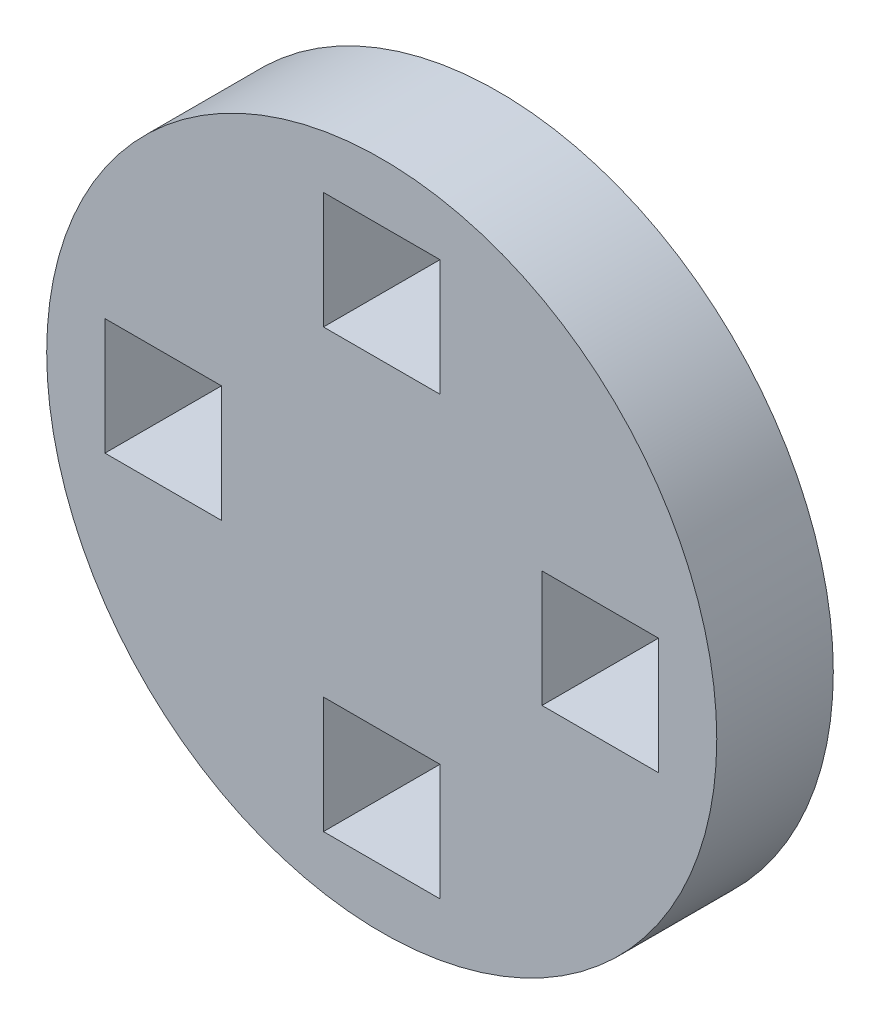
SolidWorks part; units mm, degrees
ref_plane "Front Plane" through (0, 0, 0) normal (0, 0, 1) x (1, 0, 0)
ref_plane "Top Plane" through (0, 0, 0) normal (0, 1, 0) x (1, 0, 0)
ref_plane "Right Plane" through (0, 0, 0) normal (1, 0, 0) x (0, 0, -1)
sketch "Sketch1" plane through (0, 0, 0) normal (0, 0, 1) x (1, 0, 0)
  line L0 (0, 5.5) -> (0, 0) construction
  line L1 (-2, 9.5) -> (2, 9.5)
  line L2 (-2, 9.5) -> (-2, 5.5)
  line L3 (-2, 5.5) -> (2, 5.5)
  line L4 (2, 9.5) -> (2, 5.5)
  line L5 (0, 0) -> (0, -5.5) construction
  line L6 (9.5, 2) -> (5.5, 2)
  line L7 (-2, -5.5) -> (2, -5.5)
  line L8 (-2, -5.5) -> (-2, -9.5)
  line L9 (-2, -9.5) -> (2, -9.5)
  line L10 (2, -5.5) -> (2, -9.5)
  line L11 (9.5, 2) -> (9.5, -2)
  line L12 (9.5, -2) -> (5.5, -2)
  line L13 (5.5, 2) -> (5.5, -2)
  line L14 (-5.5, 2) -> (-9.5, 2)
  line L15 (-5.5, 2) -> (-5.5, -2)
  line L16 (-5.5, -2) -> (-9.5, -2)
  line L17 (-9.5, 2) -> (-9.5, -2)
  circle A0 centre (0, 0) radius 11.5
  point P23 (0, 0)
  dimension "D1" = 23
  dimension "D2" = 4
  dimension "D3" = 11
  dimension "D4" = 2
extrude "Boss-Extrude1" add sketch "Sketch1" along normal blind 4
